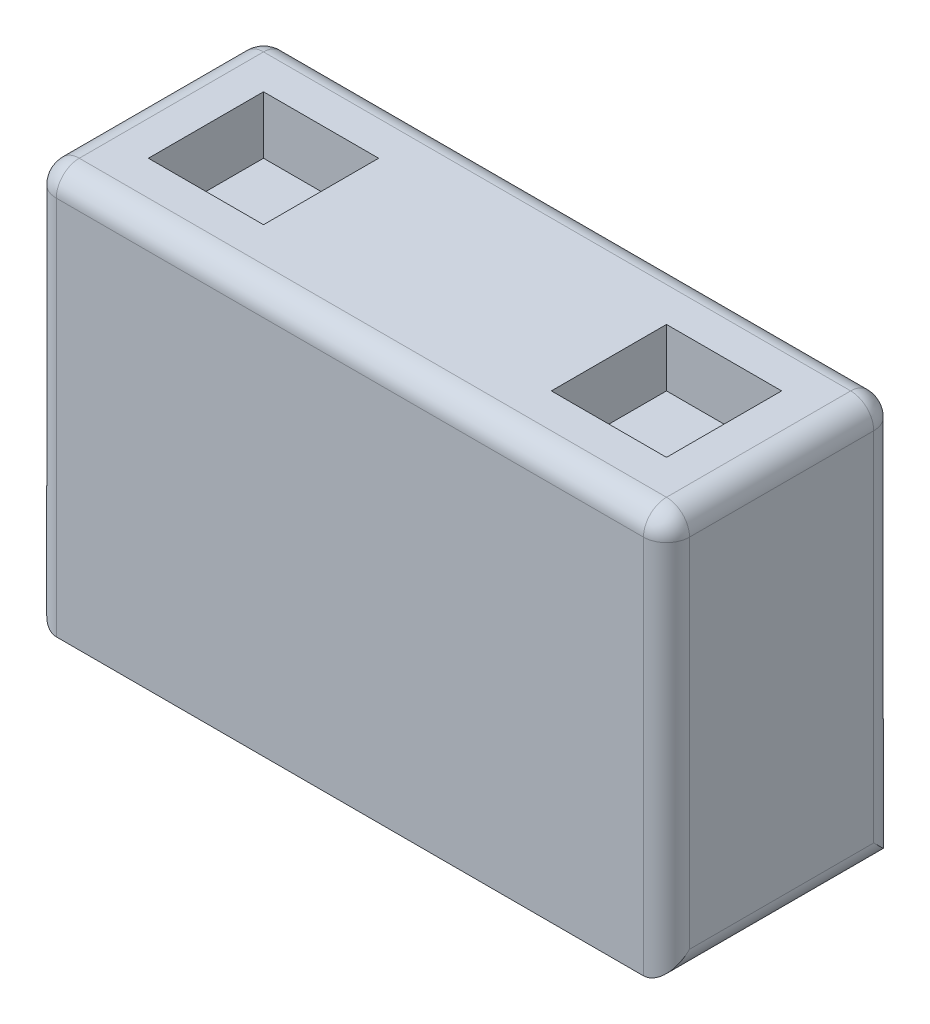
SolidWorks part; units mm, degrees
ref_plane "Front Plane" through (0, 0, 0) normal (0, 0, 1) x (1, 0, 0)
ref_plane "Top Plane" through (0, 0, 0) normal (0, 1, 0) x (1, 0, 0)
ref_plane "Right Plane" through (0, 0, 0) normal (1, 0, 0) x (0, 0, -1)
sketch "Sketch1" plane through (0, 0, 0) normal (0, 0, 1) x (1, 0, 0)
  line L0 (-27.5, 32.5) -> (27.5, 32.5)
  line L1 (27.5, 32.5) -> (27.5, -2.5)
  line L2 (21.5, -32.5) -> (-21.5, -32.5)
  line L3 (-27.5, -2.5) -> (-27.5, 32.5)
  line L4 (-27.5, -2.5) -> (-21.5, -2.5)
  line L5 (-21.5, -2.5) -> (-21.5, -32.5)
  line L7 (21.5, -32.5) -> (21.5, -2.5)
  line L8 (21.5, -2.5) -> (27.5, -2.5)
  dimension "D3" = 32.5
  dimension "D4" = 27.5
  dimension "D5" = 30
  dimension "D6" = 30
  dimension "D7" = 6
  dimension "D8" = 6
extrude "Boss-Extrude1" add sketch "Sketch1" along normal blind 20
sketch "Sketch6" plane through (0, 32.5, 0) normal (0, 1, 0) x (1, 0, 0)
  line L0 (-27.5, -20) -> (-27.5, 0) construction
  line L1 (-22.5, -5) -> (-12.5, -5)
  line L2 (-22.5, -5) -> (-22.5, -15)
  line L3 (-22.5, -15) -> (-12.5, -15)
  line L4 (-12.5, -5) -> (-12.5, -15)
  line L5 (-22.5, -5) -> (-12.5, -15) construction
  line L6 (-22.5, -15) -> (-12.5, -5) construction
  line L7 (12.5, -5) -> (22.5, -5)
  line L8 (12.5, -5) -> (12.5, -15)
  line L9 (12.5, -15) -> (22.5, -15)
  line L10 (22.5, -5) -> (22.5, -15)
  line L11 (12.5, -5) -> (22.5, -15) construction
  line L12 (12.5, -15) -> (22.5, -5) construction
  line L13 (27.5, 0) -> (-27.5, 0) construction
  line L14 (27.5, -20) -> (27.5, 0) construction
  point P0 (-17.5, -10)
  point P5 (17.5, -10)
  dimension "D1" = 10
  dimension "D2" = 10
  dimension "D3" = 10
  dimension "D4" = 10
  dimension "D5" = 10
  dimension "D6" = 10
  dimension "D7" = 10
  dimension "D8" = 10
extrude "Cut-Extrude2" cut sketch "Sketch6" against normal blind 5
sketch "Sketch7" plane through (0, -32.5, 0) normal (0, -1, 0) x (1, 0, 0)
  line L0 (-21.5, 0) -> (21.5, 0) construction
  line L1 (-19, 12.5) -> (-9, 12.5)
  line L2 (-19, 12.5) -> (-19, 2.5)
  line L3 (-19, 2.5) -> (-9, 2.5)
  line L4 (-9, 12.5) -> (-9, 2.5)
  line L5 (-19, 12.5) -> (-9, 2.5) construction
  line L6 (-19, 2.5) -> (-9, 12.5) construction
  line L7 (9, 12.5) -> (19, 12.5)
  line L8 (9, 12.5) -> (9, 2.5)
  line L9 (9, 2.5) -> (19, 2.5)
  line L10 (19, 12.5) -> (19, 2.5)
  line L11 (9, 12.5) -> (19, 2.5) construction
  line L12 (9, 2.5) -> (19, 12.5) construction
  line L13 (-21.5, 20) -> (-21.5, 0) construction
  line L14 (21.5, 20) -> (21.5, 0) construction
  point P0 (-14, 7.5)
  point P5 (14, 7.5)
  dimension "D1" = 10
  dimension "D2" = 10
  dimension "D3" = 7.5
  dimension "D4" = 7.5
  dimension "D5" = 10
  dimension "D6" = 10
  dimension "D7" = 7.5
  dimension "D8" = 7.5
extrude "Cut-Extrude3" cut sketch "Sketch7" against normal blind 5
fillet "Fillet1" radius 2 15 edges at (21.5, -17.5, 0) (27.5, 15, 0) (0, 32.5, 0) (0, 32.5, 20) (27.5, 32.5, 10) (27.5, -2.5, 10) (21.5, -17.5, 20) (27.5, 15, 20) (0, -32.5, 20) (-21.5, -32.5, 10) (-21.5, -17.5, 0) (-27.5, -2.5, 10) (-27.5, 32.5, 10) (-27.5, 15, 0) (-27.5, 15, 20)
fillet "Fillet2" radius 2 5 edges at (-20.9142, -31.9142, 0.5858) (20.9142, -31.9142, 19.4142) (21.5, -32.5, 10) (20.9142, -32.5, 0.5858) (0, -32.5, 0)
ref_plane "Plane1" through (0, -2.5, 0) normal (0, -1, 0) x (-1, 0, 0)
sketch "Sketch8" plane through (0, -2.5, 0) normal (0, -1, 0) x (-1, 0, 0)
  line L5 (-23.5443, 2.2788) -> (24.2819, 2.555)
  line L6 (24.2819, 2.555) -> (24.4372, -24.34)
  line L8 (-23.5443, -24.34) -> (-23.5443, 2.2788)
  line L9 (-23.5443, -24.34) -> (24.4372, -24.34)
extrude "Cut-Extrude4" cut sketch "Sketch8" along normal blind 30
sketch "Sketch9" plane through (0, -2.5, 0) normal (0, -1, 0) x (1, 0, 0)
  line L0 (-25.5, 20) -> (25.5, 20) construction
  line L1 (-21.5, 17.5) -> (21.5, 17.5)
  line L2 (-21.5, 17.5) -> (-21.5, 2.5)
  line L3 (-21.5, 2.5) -> (21.5, 2.5)
  line L4 (21.5, 17.5) -> (21.5, 2.5)
  line L5 (-21.5, 17.5) -> (21.5, 2.5) construction
  line L6 (-21.5, 2.5) -> (21.5, 17.5) construction
  line L7 (25.5, 0) -> (25.5, 20) construction
  point P0 (0, 10)
  point P5 (0, 0)
  dimension "D1" = 43
  dimension "D2" = 15
  dimension "D3" = 10
  dimension "D4" = 25.5
extrude "Cut-Extrude5" cut sketch "Sketch9" against normal blind 25
